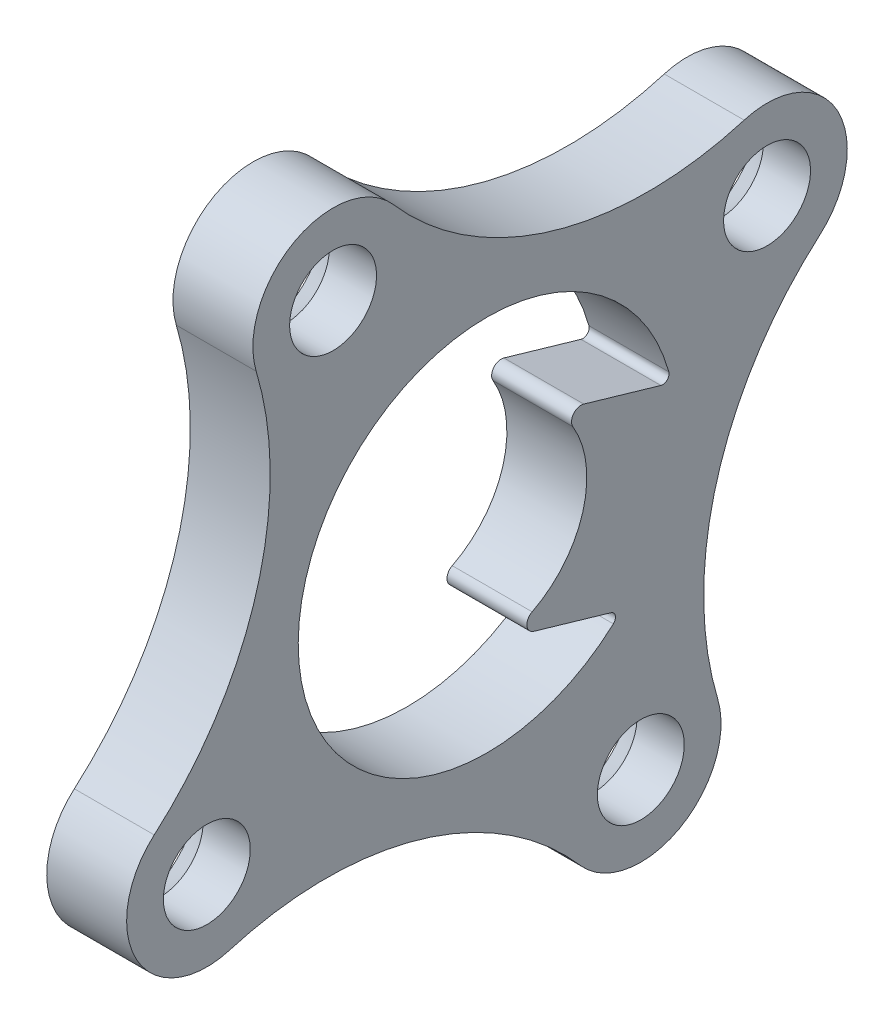
SolidWorks part; units mm, degrees
material "6061-T6 (SS)"
ref_plane "Front Plane" through (0, 0, 0) normal (0, 0, 1) x (1, 0, 0)
ref_plane "Top Plane" through (0, 0, 0) normal (0, 1, 0) x (1, 0, 0)
ref_plane "Right Plane" through (0, 0, 0) normal (1, 0, 0) x (0, 0, -1)
sketch "Sketch1" plane through (-52.0781, 0, 0) normal (-1, 0, 0) x (0, 0, 1)
  line L0 (-6.9114, 1.693) -> (-3.848, 2.5841)
  line L1 (-34.0142, 4.0065) -> (-35.1747, 4.0612) construction
  line L2 (-1.8616, -4.2449) -> (-4.925, -5.136)
  line L3 (-4.6961, -5.3339) -> (-0.0029, -3.9687) construction
  line L5 (-37.0563, -3.3999) -> (-36.7386, -3.3463) construction
  line L6 (6.1147, 11.1311) -> (-6.1147, -11.1311) construction
  line L7 (11.1311, -6.1147) -> (-11.1311, 6.1147) construction
  arc A0 (-3.848, 2.5841) -> (-3.4139, 2.0239) centre (-3.7416, 2.2182) cw
  arc A1 (-3.4139, 2.0239) -> (-1.7957, -3.5393) centre (0, 0) ccw
  arc A2 (-1.7957, -3.5393) -> (-1.8616, -4.2449) centre (-1.9681, -3.8791) cw
  circle A3 centre (0, 0) radius 3.9687 construction
  circle A4 centre (0, 0) radius 3.9687 construction
  arc A5 (-6.9114, 1.693) -> (-7.2271, 2.0048) centre (-6.9823, 1.9369) cw
  arc A6 (9.1698, 10.2214) -> (3.7082, 13.2217) centre (6.1147, 11.1311) ccw construction
  arc A7 (9.1698, 10.2214) -> (13.2217, -3.7082) centre (22.0034, 6.4003) ccw construction
  arc A8 (-7.2271, 2.0048) -> (-5.0242, -5.5684) centre (0, 0) cw
  arc A9 (-5.0242, -5.5684) -> (-4.925, -5.136) centre (-4.854, -5.3798) cw
  circle A12 centre (-11.1311, 6.1147) radius 3.175 construction
  circle A13 centre (-11.1311, 6.1147) radius 2.6924 construction
  circle A14 centre (0, 0) radius 9.525 construction
  arc A15 (10.2214, -9.1698) -> (13.2217, -3.7082) centre (11.1311, -6.1147) ccw construction
  arc A16 (10.2214, -9.1698) -> (-3.7082, -13.2217) centre (6.4003, -22.0034) ccw construction
  arc A17 (-9.1698, -10.2214) -> (-3.7082, -13.2217) centre (-6.1147, -11.1311) ccw construction
  arc A18 (-9.1698, -10.2214) -> (-13.2217, 3.7082) centre (-22.0034, -6.4003) ccw construction
  arc A19 (-10.2214, 9.1698) -> (-13.2217, 3.7082) centre (-11.1311, 6.1147) ccw construction
  arc A20 (-10.2214, 9.1698) -> (3.7082, 13.2217) centre (-6.4003, 22.0034) ccw construction
  arc A21 (9.1698, 10.2214) -> (3.7082, 13.2217) centre (6.1147, 11.1311) ccw
  arc A22 (9.1698, 10.2214) -> (13.2217, -3.7082) centre (22.0034, 6.4003) ccw
  arc A23 (10.2214, -9.1698) -> (13.2217, -3.7082) centre (11.1311, -6.1147) ccw
  arc A24 (10.2214, -9.1698) -> (-3.7082, -13.2217) centre (6.4003, -22.0034) ccw
  arc A25 (-9.1698, -10.2214) -> (-3.7082, -13.2217) centre (-6.1147, -11.1311) ccw
  arc A26 (-9.1698, -10.2214) -> (-13.2217, 3.7082) centre (-22.0034, -6.4003) ccw
  arc A27 (-10.2214, 9.1698) -> (-13.2217, 3.7082) centre (-11.1311, 6.1147) ccw
  arc A28 (-10.2214, 9.1698) -> (3.7082, 13.2217) centre (-6.4003, 22.0034) ccw
  circle A29 centre (0, 0) radius 7.5 construction
  dimension "D1" = 0.381
  dimension "D2" = 0.254
  dimension "D3" = 25.4
  dimension "D6" = 5.3848
  dimension "D7" = 19.05
  dimension "D5" = 45
  dimension "D8" = 7.112
extrude "Boss-Extrude1" add sketch "Sketch1" against normal blind 3.175
hole_wizard "CSK for #4 Flat Head Machine Screw1" positions "Sketch3" profile "Sketch4" countersink size "#4" standard "ANSI Inch" end condition up to next
sketch "Sketch3" plane through (-52.0781, 0, 0) normal (1, 0, 0) x (0, 0, -1)
  point P0 (11.1311, 6.1147)
  point P13 (-6.1147, 11.1311)
  point P16 (-11.1311, -6.1147)
  point P19 (6.1147, -11.1311)
sketch "Sketch4" plane through (-52.0781, 6.1147, -11.1311) normal (0, 1, 0) x (0, 0, 1)
  line L0 (0, 0) -> (0, 3.175)
  line L1 (0, 3.175) -> (1.7272, 3.175)
  line L2 (1.7272, 3.175) -> (1.7272, 1.3003)
  line L3 (1.7272, 1.3003) -> (2.8575, 0)
  line L5 (2.8575, 0) -> (0, 0)
  line L6 (-1.7272, 1.3003) -> (-2.8575, 0) construction
  line L11 (0, -6.35) -> (0, 107.95) construction
  dimension "Thru Hole Dia." = 3.4544
  dimension "Thru Hole Depth" = 3.175
  dimension "Near C'Sink Dia." = 5.715
  dimension "Near C'Sink Angle" = 82
